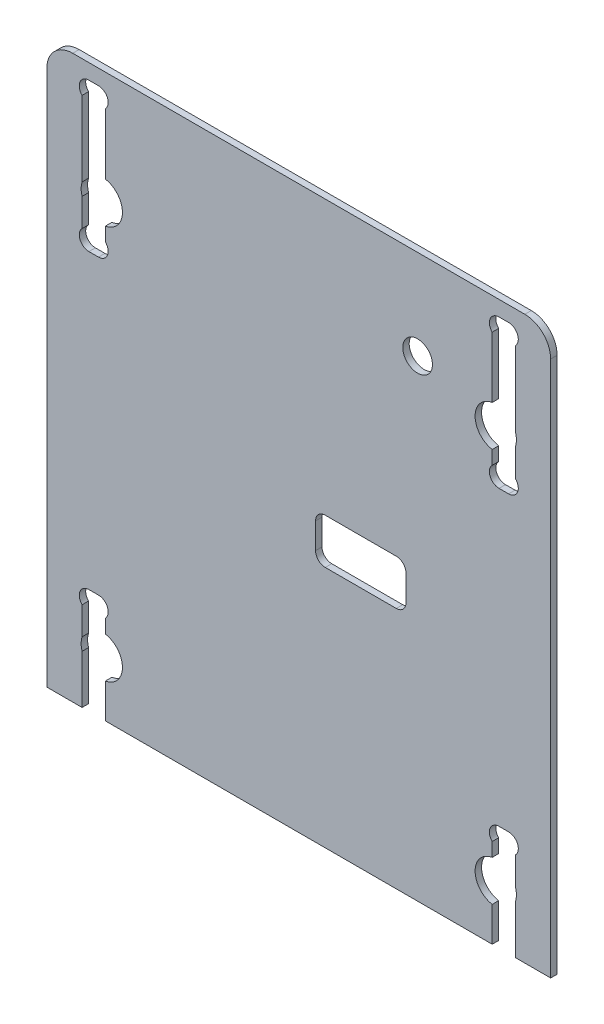
SolidWorks part; units mm, degrees
ref_plane "Front Plane" through (0, 0, 0) normal (0, 0, 1) x (1, 0, 0)
ref_plane "Top Plane" through (0, 0, 0) normal (0, 1, 0) x (1, 0, 0)
ref_plane "Right Plane" through (0, 0, 0) normal (1, 0, 0) x (0, 0, -1)
sketch "Sketch1" plane through (0, 0, 0) normal (0, 0, 1) x (1, 0, 0)
  line L1 (19.5, -7.325) -> (19.5, 4.675)
  line L2 (19.5, 24) -> (-19.5, 24)
  line L4 (16.75, 22.5) -> (15, 22.5) construction
  line L7 (14.975, 13.6738) -> (14.975, 12.6107)
  line L8 (14.975, 21.5393) -> (14.975, 16.8262)
  line L9 (16.2447, 22.8197) -> (15.5053, 22.8197)
  line L10 (16.775, 15.7341) -> (16.775, 21.5393)
  line L11 (16.775, 12.6107) -> (16.775, 14.7659)
  line L12 (15.5053, 11.3303) -> (16.2447, 11.3303)
  line L13 (14.975, 13.6738) -> (14.975, 12.6107)
  line L14 (14.975, 21.5393) -> (14.975, 16.8262)
  line L15 (16.2447, 22.8197) -> (15.5053, 22.8197)
  line L16 (16.775, 15.7341) -> (16.775, 21.5393)
  line L17 (16.775, 12.6107) -> (16.775, 14.7659)
  line L18 (15.5053, 11.3303) -> (16.2447, 11.3303)
  line L19 (-16.775, 14.7659) -> (-16.775, 12.6107)
  line L20 (-16.775, 21.5393) -> (-16.775, 15.7341)
  line L21 (-15.5053, 22.8197) -> (-16.2447, 22.8197)
  line L22 (-14.975, 16.8262) -> (-14.975, 21.5393)
  line L23 (-14.975, 12.6107) -> (-14.975, 13.6738)
  line L24 (-16.2447, 11.3303) -> (-15.5053, 11.3303)
  line L25 (-16.775, 14.7659) -> (-16.775, 12.6107)
  line L26 (-16.775, 21.5393) -> (-16.775, 15.7341)
  line L27 (-15.5053, 22.8197) -> (-16.2447, 22.8197)
  line L28 (-14.975, 16.8262) -> (-14.975, 21.5393)
  line L29 (-14.975, 12.6107) -> (-14.975, 13.6738)
  line L30 (-16.2447, 11.3303) -> (-15.5053, 11.3303)
  line L33 (-19.5, -19.5) -> (-16.775, -19.5)
  line L34 (-16.775, -19.5) -> (-16.775, -15.7341)
  line L35 (-16.775, -14.7659) -> (-16.775, -12.6107)
  line L36 (-16.2447, -11.3303) -> (-15.5053, -11.3303)
  line L37 (-14.975, -12.6107) -> (-14.975, -13.6738)
  line L38 (-14.975, -16.8262) -> (-14.975, -19.5)
  line L39 (-14.975, -19.5) -> (14.975, -19.5)
  line L40 (14.975, -19.5) -> (14.975, -16.8262)
  line L41 (14.975, -13.6738) -> (14.975, -12.6107)
  line L42 (15.5053, -11.3303) -> (16.2447, -11.3303)
  line L43 (16.775, -12.6107) -> (16.775, -14.7659)
  line L44 (16.775, -15.7341) -> (16.775, -19.5)
  line L45 (16.775, -19.5) -> (19.5, -19.5)
  line L46 (19.5, -19.5) -> (19.5, -7.325)
  line L47 (19.5, -7.325) -> (17.5, -7.325)
  line L48 (17.5, -7.325) -> (17.5, -9.4)
  line L49 (16.75, -10.15) -> (13.05, -10.15)
  line L50 (12.3, -10.9) -> (12.3, -16.7496)
  line L51 (11.55, -17.4996) -> (-11.55, -17.4996)
  line L52 (-12.3, -16.7496) -> (-12.3, -10.9)
  line L53 (-13.05, -10.15) -> (-16.75, -10.15)
  line L54 (-17.5, -9.4) -> (-17.5, 9.4)
  line L55 (-16.75, 10.15) -> (-13.05, 10.15)
  line L56 (-12.3, 10.9) -> (-12.3, 16.7496)
  line L57 (-11.55, 17.4996) -> (6.3156, 17.4996)
  line L58 (9.2, 14.9) -> (11.55, 14.9)
  line L59 (12.3, 14.15) -> (12.3, 10.9)
  line L60 (13.05, 10.15) -> (16.75, 10.15)
  line L61 (17.5, 9.4) -> (17.5, 4.675)
  line L62 (17.5, 4.675) -> (19.5, 4.675)
  line L63 (19.5, 4.675) -> (19.5, 35.2)
  line L64 (15.5, 39.2) -> (-15.5, 39.2)
  line L65 (-19.5, 35.2) -> (-19.5, -19.5)
  line L66 (-19.5, -19.5) -> (-16.775, -19.5)
  line L67 (-16.775, -19.5) -> (-16.775, -15.7341)
  line L68 (-16.775, -14.7659) -> (-16.775, -12.6107)
  line L69 (-16.2447, -11.3303) -> (-15.5053, -11.3303)
  line L70 (-14.975, -12.6107) -> (-14.975, -13.6738)
  line L71 (-14.975, -16.8262) -> (-14.975, -19.5)
  line L72 (-14.975, -19.5) -> (14.975, -19.5)
  line L73 (14.975, -19.5) -> (14.975, -16.8262)
  line L74 (14.975, -13.6738) -> (14.975, -12.6107)
  line L75 (15.5053, -11.3303) -> (16.2447, -11.3303)
  line L76 (16.775, -12.6107) -> (16.775, -14.7659)
  line L77 (16.775, -15.7341) -> (16.775, -19.5)
  line L78 (16.775, -19.5) -> (19.5, -19.5)
  line L79 (19.5, -19.5) -> (19.5, -7.325)
  line L80 (19.5, -7.325) -> (17.5, -7.325)
  line L81 (17.5, -7.325) -> (17.5, -9.4)
  line L82 (16.75, -10.15) -> (13.05, -10.15)
  line L83 (12.3, -10.9) -> (12.3, -16.7496)
  line L84 (11.55, -17.4996) -> (-11.55, -17.4996)
  line L85 (-12.3, -16.7496) -> (-12.3, -10.9)
  line L86 (-13.05, -10.15) -> (-16.75, -10.15)
  line L87 (-17.5, -9.4) -> (-17.5, 9.4)
  line L88 (-16.75, 10.15) -> (-13.05, 10.15)
  line L89 (-12.3, 10.9) -> (-12.3, 16.7496)
  line L90 (-11.55, 17.4996) -> (6.3156, 17.4996)
  line L91 (9.2, 14.9) -> (11.55, 14.9)
  line L92 (12.3, 14.15) -> (12.3, 10.9)
  line L93 (13.05, 10.15) -> (16.75, 10.15)
  line L94 (17.5, 9.4) -> (17.5, 4.675)
  line L95 (17.5, 4.675) -> (19.5, 4.675)
  line L96 (19.5, 4.675) -> (19.5, 35.2)
  line L97 (15.5, 39.2) -> (-15.5, 39.2)
  line L98 (-19.5, 35.2) -> (-19.5, -19.5)
  circle A5 centre (9.2, 17.05) radius 1.15 construction
  circle A6 centre (9.2, 17.05) radius 1.15
  arc A17 (14.975, 12.6107) -> (15.5053, 11.3303) centre (15.5053, 12.0803) ccw
  arc A18 (14.975, 16.8262) -> (14.975, 13.6738) centre (15.25, 15.25) ccw
  arc A19 (15.5053, 22.8197) -> (14.975, 21.5393) centre (15.5053, 22.0697) ccw
  arc A20 (16.775, 21.5393) -> (16.2447, 22.8197) centre (16.2447, 22.0697) ccw
  arc A21 (16.775, 14.7659) -> (16.775, 15.7341) centre (15.25, 15.25) ccw
  arc A22 (16.2447, 11.3303) -> (16.775, 12.6107) centre (16.2447, 12.0803) ccw
  arc A23 (14.975, 12.6107) -> (15.5053, 11.3303) centre (15.5053, 12.0803) ccw
  arc A24 (14.975, 16.8262) -> (14.975, 13.6738) centre (15.25, 15.25) ccw
  arc A25 (15.5053, 22.8197) -> (14.975, 21.5393) centre (15.5053, 22.0697) ccw
  arc A26 (16.775, 21.5393) -> (16.2447, 22.8197) centre (16.2447, 22.0697) ccw
  arc A27 (16.775, 14.7659) -> (16.775, 15.7341) centre (15.25, 15.25) ccw
  arc A28 (16.2447, 11.3303) -> (16.775, 12.6107) centre (16.2447, 12.0803) ccw
  arc A29 (-16.775, 12.6107) -> (-16.2447, 11.3303) centre (-16.2447, 12.0803) ccw
  arc A30 (-16.775, 15.7341) -> (-16.775, 14.7659) centre (-15.25, 15.25) ccw
  arc A31 (-16.2447, 22.8197) -> (-16.775, 21.5393) centre (-16.2447, 22.0697) ccw
  arc A32 (-14.975, 21.5393) -> (-15.5053, 22.8197) centre (-15.5053, 22.0697) ccw
  arc A33 (-16.775, -14.7659) -> (-16.775, -15.7341) centre (-15.25, -15.25) ccw
  arc A34 (-16.2447, -11.3303) -> (-16.775, -12.6107) centre (-16.2447, -12.0803) ccw
  arc A35 (-14.975, -12.6107) -> (-15.5053, -11.3303) centre (-15.5053, -12.0803) ccw
  arc A36 (-14.975, -16.8262) -> (-14.975, -13.6738) centre (-15.25, -15.25) ccw
  arc A37 (14.975, -13.6738) -> (14.975, -16.8262) centre (15.25, -15.25) ccw
  arc A38 (15.5053, -11.3303) -> (14.975, -12.6107) centre (15.5053, -12.0803) ccw
  arc A39 (16.775, -12.6107) -> (16.2447, -11.3303) centre (16.2447, -12.0803) ccw
  arc A40 (16.775, -15.7341) -> (16.775, -14.7659) centre (15.25, -15.25) ccw
  arc A41 (16.75, -10.15) -> (17.5, -9.4) centre (16.75, -9.4) ccw
  arc A42 (13.05, -10.15) -> (12.3, -10.9) centre (13.05, -10.9) ccw
  arc A43 (11.55, -17.4996) -> (12.3, -16.7496) centre (11.55, -16.7496) ccw
  arc A44 (-12.3, -16.7496) -> (-11.55, -17.4996) centre (-11.55, -16.7496) ccw
  arc A45 (-12.3, -10.9) -> (-13.05, -10.15) centre (-13.05, -10.9) ccw
  arc A46 (-17.5, -9.4) -> (-16.75, -10.15) centre (-16.75, -9.4) ccw
  arc A47 (-16.75, 10.15) -> (-17.5, 9.4) centre (-16.75, 9.4) ccw
  arc A48 (-13.05, 10.15) -> (-12.3, 10.9) centre (-13.05, 10.9) ccw
  arc A49 (-11.55, 17.4996) -> (-12.3, 16.7496) centre (-11.55, 16.7496) ccw
  arc A50 (7.0616, 16.8273) -> (6.3156, 17.4996) centre (6.3156, 16.7496) ccw
  arc A51 (7.0616, 16.8273) -> (9.2, 14.9) centre (9.2, 17.05) ccw
  arc A52 (12.3, 14.15) -> (11.55, 14.9) centre (11.55, 14.15) ccw
  arc A53 (12.3, 10.9) -> (13.05, 10.15) centre (13.05, 10.9) ccw
  arc A54 (17.5, 9.4) -> (16.75, 10.15) centre (16.75, 9.4) ccw
  arc A55 (19.5, 35.2) -> (15.5, 39.2) centre (15.5, 35.2) ccw
  arc A56 (-15.5, 39.2) -> (-19.5, 35.2) centre (-15.5, 35.2) ccw
  arc A57 (-16.775, -14.7659) -> (-16.775, -15.7341) centre (-15.25, -15.25) ccw
  arc A58 (-16.2447, -11.3303) -> (-16.775, -12.6107) centre (-16.2447, -12.0803) ccw
  arc A59 (-14.975, -12.6107) -> (-15.5053, -11.3303) centre (-15.5053, -12.0803) ccw
  arc A60 (-14.975, -16.8262) -> (-14.975, -13.6738) centre (-15.25, -15.25) ccw
  arc A61 (14.975, -13.6738) -> (14.975, -16.8262) centre (15.25, -15.25) ccw
  arc A62 (15.5053, -11.3303) -> (14.975, -12.6107) centre (15.5053, -12.0803) ccw
  arc A63 (16.775, -12.6107) -> (16.2447, -11.3303) centre (16.2447, -12.0803) ccw
  arc A64 (16.775, -15.7341) -> (16.775, -14.7659) centre (15.25, -15.25) ccw
  arc A65 (16.75, -10.15) -> (17.5, -9.4) centre (16.75, -9.4) ccw
  arc A66 (13.05, -10.15) -> (12.3, -10.9) centre (13.05, -10.9) ccw
  arc A67 (11.55, -17.4996) -> (12.3, -16.7496) centre (11.55, -16.7496) ccw
  arc A68 (-12.3, -16.7496) -> (-11.55, -17.4996) centre (-11.55, -16.7496) ccw
  arc A69 (-12.3, -10.9) -> (-13.05, -10.15) centre (-13.05, -10.9) ccw
  arc A70 (-17.5, -9.4) -> (-16.75, -10.15) centre (-16.75, -9.4) ccw
  arc A71 (-16.75, 10.15) -> (-17.5, 9.4) centre (-16.75, 9.4) ccw
  arc A72 (-13.05, 10.15) -> (-12.3, 10.9) centre (-13.05, 10.9) ccw
  arc A73 (-11.55, 17.4996) -> (-12.3, 16.7496) centre (-11.55, 16.7496) ccw
  arc A74 (7.0616, 16.8273) -> (6.3156, 17.4996) centre (6.3156, 16.7496) ccw
  arc A75 (7.0616, 16.8273) -> (9.2, 14.9) centre (9.2, 17.05) ccw
  arc A76 (12.3, 14.15) -> (11.55, 14.9) centre (11.55, 14.15) ccw
  arc A77 (12.3, 10.9) -> (13.05, 10.15) centre (13.05, 10.9) ccw
  arc A78 (17.5, 9.4) -> (16.75, 10.15) centre (16.75, 9.4) ccw
  arc A79 (19.5, 35.2) -> (15.5, 39.2) centre (15.5, 35.2) ccw
  arc A80 (-15.5, 39.2) -> (-19.5, 35.2) centre (-15.5, 35.2) ccw
  arc A81 (-14.975, 13.6738) -> (-14.975, 16.8262) centre (-15.25, 15.25) ccw
  arc A82 (-15.5053, 11.3303) -> (-14.975, 12.6107) centre (-15.5053, 12.0803) ccw
  arc A83 (-16.775, 12.6107) -> (-16.2447, 11.3303) centre (-16.2447, 12.0803) ccw
  arc A84 (-16.775, 15.7341) -> (-16.775, 14.7659) centre (-15.25, 15.25) ccw
  arc A85 (-16.2447, 22.8197) -> (-16.775, 21.5393) centre (-16.2447, 22.0697) ccw
  arc A86 (-14.975, 21.5393) -> (-15.5053, 22.8197) centre (-15.5053, 22.0697) ccw
  arc A87 (-14.975, 13.6738) -> (-14.975, 16.8262) centre (-15.25, 15.25) ccw
  arc A88 (-15.5053, 11.3303) -> (-14.975, 12.6107) centre (-15.5053, 12.0803) ccw
  dimension "D2" = 0
  dimension "D4" = 1.5
  dimension "D1" = 0
  dimension "D3" = 0
extrude "Shape" add sketch "Sketch1" along normal blind 0.5 contours A88 L30 A83 L25 A84 L26 A85 L2 L98 L66 L67 A57 L68 A58 L69 A59 L70 A60 L71 L72 L73 A61 L74 A62 L75 A63 L76 A64 L77 L78 L79 L80 L81 A65 L82 A66 L83 A67 L84 A68 L85 A69 L86 A70 L87 A71 L88 A72 L89 A73 L90 | L94 A78 L93 A77 L92 A76 L91 A75 A74 L90 A73 L89 A72 L88 A71 L87 A70 L86 A69 L85 A68 L84 A67 L83 A66 L82 A65 L81 L80 L1 L95 region at (0.2943, -0.2209, 0) region at (18.9158, -13.4125, 0)
sketch "Sketch2" plane through (0, 0, 0.5) normal (0, 0, 1) x (1, 0, 0)
  line L0 (9.3, 6.3018) -> (0.3, 6.3018) construction
  line L1 (9.3, 6.3018) -> (0.3, 6.3018)
  line L2 (4.8, 6.3018) -> (4.8, -19.5) construction
  line L3 (-14.975, -19.5) -> (14.975, -19.5) construction
  line L5 (2.05, -0.6982) -> (7.55, -0.6982)
  line L6 (1.3, 0.0518) -> (1.3, 2.0518)
  line L7 (2.05, 2.8018) -> (7.55, 2.8018)
  line L8 (8.3, 0.0518) -> (8.3, 2.0518)
  line L9 (1.3, -0.6982) -> (8.3, 2.8018) construction
  line L10 (1.3, 2.8018) -> (8.3, -0.6982) construction
  arc A0 (7.55, 2.8018) -> (8.3, 2.0518) centre (7.55, 2.0518) cw
  arc A1 (7.55, -0.6982) -> (8.3, 0.0518) centre (7.55, 0.0518) ccw
  arc A2 (2.05, -0.6982) -> (1.3, 0.0518) centre (2.05, 0.0518) cw
  arc A3 (1.3, 2.0518) -> (2.05, 2.8018) centre (2.05, 2.0518) cw
  point P6 (4.8, 1.0518)
  dimension "D4" = 0.75
  dimension "D1" = 7
  dimension "D2" = 3.5
  dimension "D3" = 3.5
extrude "Camera connector hole" cut sketch "Sketch2" against normal up to next contours L5 L8 L7 L6 region at (4.8, 1.0518, 0.5)
fillet "Fillet1" radius 2 2 edges at (19.5, 24, 0.25) (-19.5, 24, 0.25)
